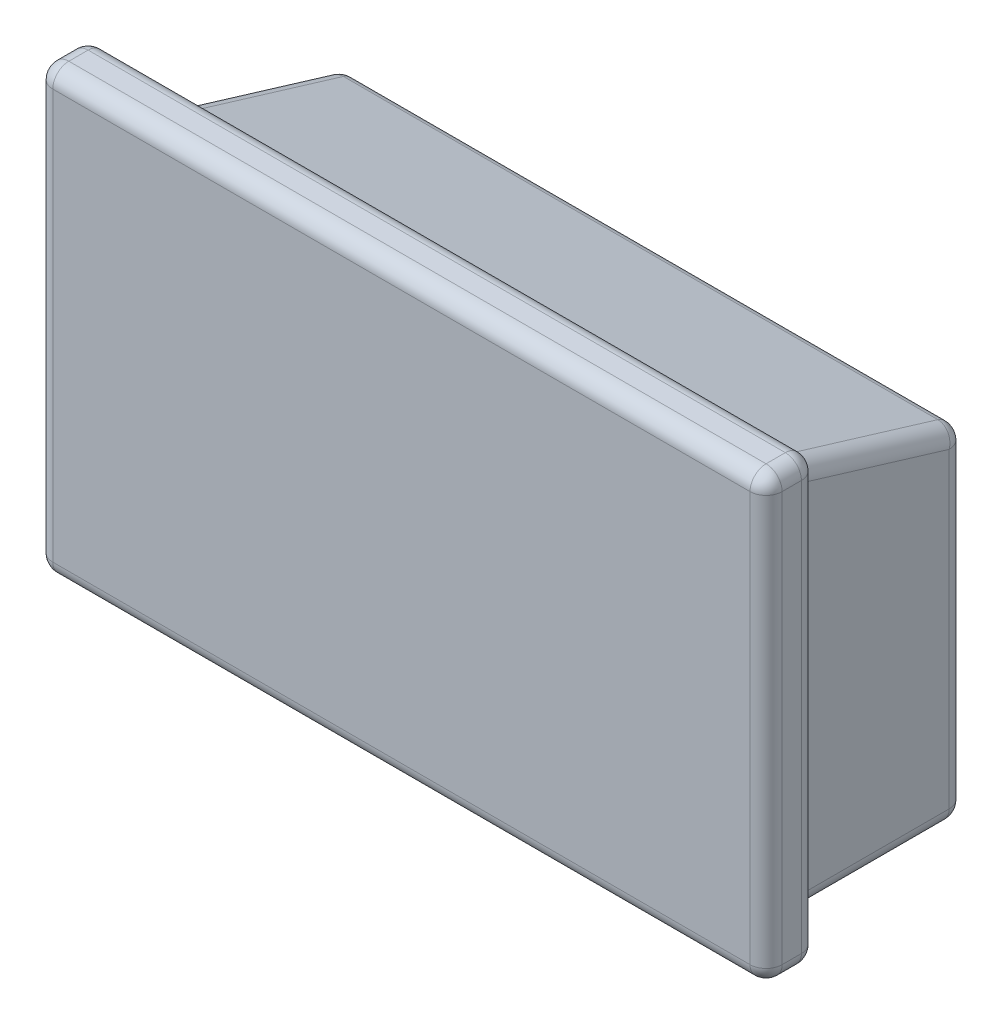
SolidWorks part; units mm, degrees
material "PVC Rigid"
ref_plane "Front Plane" through (0, 0, 0) normal (0, 0, 1) x (1, 0, 0)
ref_plane "Top Plane" through (0, 0, 0) normal (0, 1, 0) x (1, 0, 0)
ref_plane "Right Plane" through (0, 0, 0) normal (1, 0, 0) x (0, 0, -1)
sketch "Sketch1" plane through (0, 0, 0) normal (0, 0, 1) x (1, 0, 0)
  line L1 (0, 0) -> (454, 0)
  line L2 (0, 0) -> (0, 275)
  line L3 (0, 275) -> (454, 275)
  line L4 (454, 0) -> (454, 275)
  dimension "D1" = 275
  dimension "D2" = 454
extrude "Boss-Extrude1" add sketch "Sketch1" against normal blind 156
sketch "Sketch2" plane through (454, 0, 0) normal (1, 0, 0) x (0, 0, -1)
  line L3 (156, 0) -> (156, 275) construction
  line L4 (156, 211.1876) -> (32, 248.761)
  line L5 (32, 248.761) -> (32, 275)
  line L6 (156, 275) -> (0, 275) construction
  line L8 (156, 275) -> (32, 275)
  line L9 (156, 275) -> (156, 211.1876)
  line L10 (0, 0) -> (0, 275) construction
  dimension "D1" = 32
extrude "Cut-Extrude1" cut sketch "Sketch2" against normal through all
sketch "Sketch3" plane through (0, 0, -156) normal (0, 0, -1) x (-1, 0, 0)
  line L2 (-454, 0) -> (-422, 0)
  line L3 (-454, 0) -> (-454, 275)
  line L4 (-454, 275) -> (-422, 275)
  line L5 (-422, 0) -> (-422, 275)
  line L6 (0, 0) -> (-32, 0)
  line L7 (0, 0) -> (0, 275)
  line L8 (0, 275) -> (-32, 275)
  line L9 (-32, 0) -> (-32, 275)
  dimension "D1" = 275
  dimension "D2" = 32
  dimension "D3" = 275
  dimension "D4" = 32
extrude "Cut-Extrude2" cut sketch "Sketch3" along direction (0, 0, 1) on the side against the normal up to surface (124 mm away) up to face at (227, 261.8805, -32)
fillet "Fillet2" radius 10 24 edges at (227, 248.761, -32) (32, 124.3805, -32) (16, 0, -32) (422, 124.3805, -32) (438, 0, -32) (422, 229.9743, -94) (422, 0, -94) (454, 0, -16) (454, 137.5, -32) (227, 275, -32) (454, 275, -16) (32, 0, -94) (227, 0, -156) (422, 105.5938, -156) (227, 211.1876, -156) (32, 229.9743, -94) (32, 105.5938, -156) (0, 0, -16) (227, 0, 0) (227, 275, 0) (0, 137.5, -32) (0, 275, -16) (0, 137.5, 0) (454, 137.5, 0)
